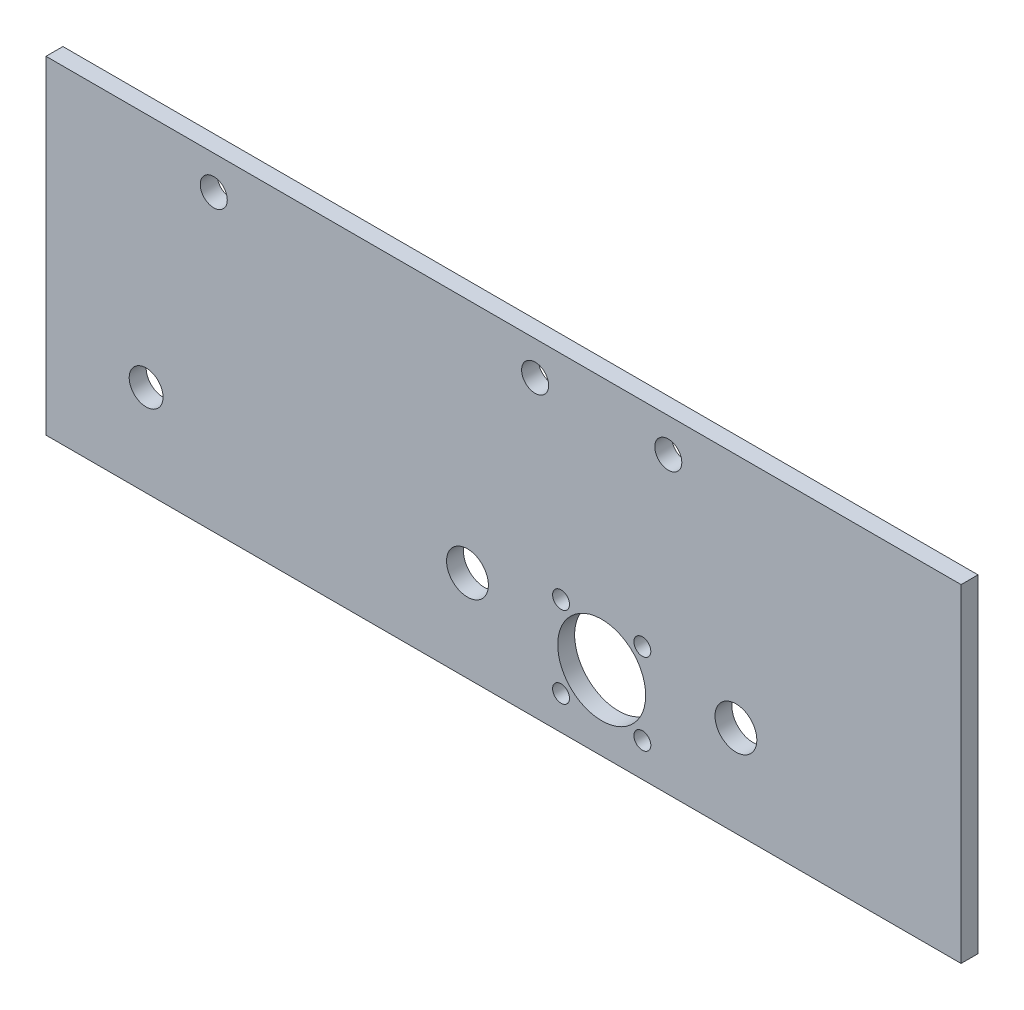
SolidWorks part; units mm, degrees
ref_plane "Спереди" through (0, 0, 0) normal (0, 0, 1) x (1, 0, 0)
ref_plane "Сверху" through (0, 0, 0) normal (0, 1, 0) x (1, 0, 0)
ref_plane "Справа" through (0, 0, 0) normal (1, 0, 0) x (0, 0, -1)
sketch "Эскиз1" plane through (0, 0, 0) normal (0, 0, 1) x (1, 0, 0)
  line L0 (-12.0208, 12.0208) -> (0, 0) construction
  line L1 (-164.3075, 75) -> (106.2638, 75)
  line L2 (-164.3075, 75) -> (-164.3075, -22.0208)
  line L3 (-164.3075, -22.0208) -> (106.2638, -22.0208)
  line L4 (106.2638, 75) -> (106.2638, -22.0208)
  line L5 (0, 0) -> (0, 75) construction
  line L6 (-39.6863, 5) -> (0, 0) construction
  circle A0 centre (0, 0) radius 13
  circle A1 centre (-12.0208, 12.0208) radius 2.5
  circle A2 centre (12.0208, 12.0208) radius 2.5
  circle A3 centre (12.0208, -12.0208) radius 2.5
  circle A4 centre (-12.0208, -12.0208) radius 2.5
  circle A5 centre (-39.6863, 5) radius 6.1833
  circle A6 centre (39.6863, 5) radius 6.1833
  circle A7 centre (-134.7052, 5) radius 5
  circle A8 centre (-19.6863, 65) radius 4
  circle A9 centre (19.6863, 65) radius 4
  circle A10 centre (-114.7052, 65) radius 4
  point P19 (0, 0)
  point P29 (-0.1499, 0.1499)
  point P30 (-36.3786, 16.6313)
  point P31 (-114.7052, 65)
  dimension "D2" = 5
  dimension "D4" = 26
  dimension "D9" = 8
  dimension "D1" = 45
  dimension "D3" = 17
  dimension "D6" = 60
  dimension "D7" = 20
  dimension "D8" = 20
  dimension "D10" = 10
  dimension "D11" = 10
  dimension "D12" = 40
  dimension "D13" = 5
  dimension "D5" = 4
extrude "Бобышка-Вытянуть1" add sketch "Эскиз1" along normal blind 5
equation "\"Диаметр резьбы редуктора\" = 4  'Диаметр резьбы на фланце"
equation "\"Глубина резьбы редуктора\" = 7  'Диаметр резьбы на фланце"
equation "\"Диаметр окружности расположения редуктора\" = 34  'Диаметр расположения резьбы на фланце"
equation "\"Диаметр бурта редуктора\" = 26  'Диаметр бурта на фланце (Посадка h7)"
equation "\"Угл сдвига редуктора\" = 45"
equation "\"D1@Эскиз1\"=\"Угл сдвига редуктора\""
equation "\"D2@Эскиз1\"=\"Диаметр резьбы редуктора\"+1"
equation "\"D3@Эскиз1\"=\"Диаметр окружности расположения редуктора\"/2"
equation "\"D4@Эскиз1\"=\"Диаметр бурта редуктора\""
equation "\"Толщина пластины\" = 5"
equation "\"Межосевое прижима Вертикаль\" = 20  '!!!"
equation "\"Межосевое прижима Горизонталь\" = 20  '!!!"
equation "\"D7@Эскиз1\"=\"Межосевое прижима Горизонталь\""
equation "\"D8@Эскиз1\"=\"Межосевое прижима Горизонталь\""
equation "\"D1@Бобышка-Вытянуть1\"=\"Толщина пластины\""
equation "\"D6@Эскиз1\"=\"Межосевое прижима Вертикаль\"+\"Внешний диаметр ролика\""
equation "\"Внешний диаметр ролика\" = 40  'Внешний диаметр ролика"
equation "\"Диаметр вала ролика\" = 8  '!!!"
equation "\"D9@Эскиз1\"=\"Диаметр вала ролика\""
